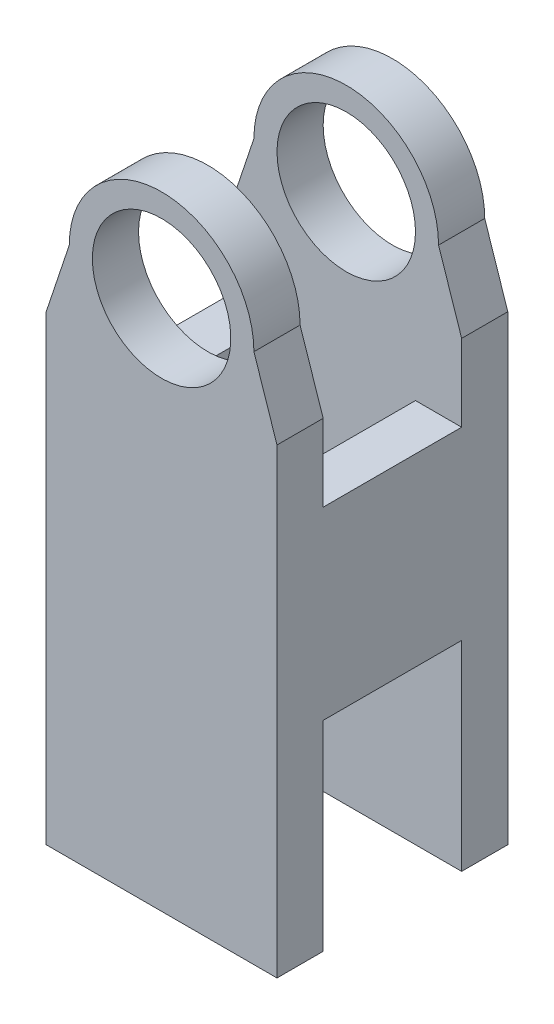
SolidWorks part; units mm, degrees
ref_plane "Front Plane" through (0, 0, 0) normal (0, 0, 1) x (1, 0, 0)
ref_plane "Top Plane" through (0, 0, 0) normal (0, 1, 0) x (1, 0, 0)
ref_plane "Right Plane" through (0, 0, 0) normal (1, 0, 0) x (0, 0, -1)
sketch "Sketch1" plane through (0, 0, 0) normal (0, 1, 0) x (1, 0, 0)
  line L0 (4.5, -4.5) -> (4.5, 4.5)
  line L1 (7.5, -7.5) -> (-7.5, -7.5)
  line L2 (7.5, -7.5) -> (7.5, 7.5)
  line L3 (7.5, 7.5) -> (-7.5, 7.5)
  line L4 (-7.5, -7.5) -> (-7.5, 7.5)
  line L5 (7.5, -7.5) -> (-7.5, 7.5) construction
  line L6 (7.5, 7.5) -> (-7.5, -7.5) construction
  line L7 (4.5, 4.5) -> (-4.5, 4.5)
  line L8 (-4.5, -4.5) -> (-4.5, 4.5)
  line L9 (4.5, -4.5) -> (-4.5, -4.5)
  point P0 (0, 0)
  dimension "D1" = 15
  dimension "D2" = 15
  dimension "D3" = 3
extrude "Boss-Extrude1" add sketch "Sketch1" along normal blind 30
sketch "Sketch3" plane through (0, 0, -7.5) normal (0, 0, -1) x (-1, 0, 0)
  line L0 (-7.5, 30) -> (7.5, 30) construction
  line L1 (-6, 34.5) -> (-7.5, 30)
  line L2 (-7.5, 30) -> (7.5, 30)
  line L3 (7.5, 30) -> (6, 34.5)
  line L4 (7.5, 30) -> (7.5, 0) construction
  line L5 (-7.5, 30) -> (7.5, 30)
  line L6 (-7.5, 30) -> (-7.5, 29)
  line L7 (-7.5, 29) -> (7.5, 29)
  line L8 (7.5, 30) -> (7.5, 29)
  circle A0 centre (0, 34.5) radius 4.5
  arc A1 (-6, 34.5) -> (6, 34.5) centre (0, 34.5) cw
  line M10 (7.5, 0) -> (7.5, 30)
  line M11 (7.5, 30) -> (-7.5, 30)
  line M12 (-7.5, 30) -> (-7.5, 0)
  dimension "D1" = 9
  dimension "D2" = 6
  dimension "D3" = 1
extrude "Boss-Extrude3" add sketch "Sketch3" against normal up to surface (3 mm away) contours A1 L1 L5 A0 L3 M11 | L7 L5 M12 M10 M11 region at (0, 40.3169, -7.5) region at (0, 29.5, -7.5) up to face at (0, 15, -4.5)
extrude "Boss-Extrude4" add sketch "Sketch3<4>" along normal up to surface (-12 mm away) from surface contours A1 L1 L5 A0 L3 M11 | L7 L5 M12 M10 M11 region at (0, 40.3169, -7.5) region at (0, 29.5, -7.5) up to face at (0, 15, 4.5) starting at face at (0, 15, 7.5)
sketch "Sketch3<4>" plane through (0, 0, -7.5) normal (0, 0, -1) x (-1, 0, 0) same geometry as "Sketch3"
sketch "Sketch5" plane through (7.5, 0, 0) normal (1, 0, 0) x (0, 0, -1)
  line L1 (-4.5, 0) -> (4.5, 0)
  line L2 (-4.5, 0) -> (-4.5, 13)
  line L3 (-4.5, 13) -> (4.5, 13)
  line L4 (-4.5, 0) -> (4.5, 0)
  line L5 (-4.5, 30) -> (-4.5, 0)
  line L6 (4.5, 30) -> (-4.5, 30)
  line L7 (4.5, 0) -> (4.5, 30)
  line L8 (-4.5, 0) -> (4.5, 0) construction
  line L9 (-4.5, 30) -> (-4.5, 0) construction
  line L10 (4.5, 30) -> (-4.5, 30) construction
  line L11 (4.5, 0) -> (4.5, 30) construction
  line L12 (4.5, 0) -> (4.5, 13)
  dimension "D2" = 13
  dimension "D1" = 0
extrude "Cut-Extrude2" cut sketch "Sketch5" against normal up to next
sketch "Sketch6" plane through (0, 0, -4.5) normal (0, 0, 1) x (1, 0, 0)
  line L0 (7.5, 13) -> (7.5, 0) construction
  line L1 (7.5, 13) -> (7.5, 0) construction
  line L2 (7.5, 13) -> (-7.5, 13) construction
  line L3 (-7.5, 30) -> (-7.5, 0) construction
  circle A0 centre (0, 11) radius 2
  point P4 (0, 0)
  dimension "D1" = 4
extrude "Boss-Extrude6" add sketch "Sketch6" along normal up to surface (9 mm away) up to face at (1.5, 22.1, 4.5)
sketch "Sketch7" plane through (7.5, 0, 0) normal (1, 0, 0) x (0, 0, -1)
  line L0 (-4.5, 34.5) -> (-4.5, 30) construction
  line L1 (4.5, 30) -> (-4.5, 30)
  line L2 (4.5, 30) -> (4.5, 25)
  line L3 (4.5, 25) -> (-4.5, 25)
  line L4 (-4.5, 30) -> (-4.5, 25)
  dimension "D1" = 5
extrude "Cut-Extrude3" cut sketch "Sketch7" against normal through all
